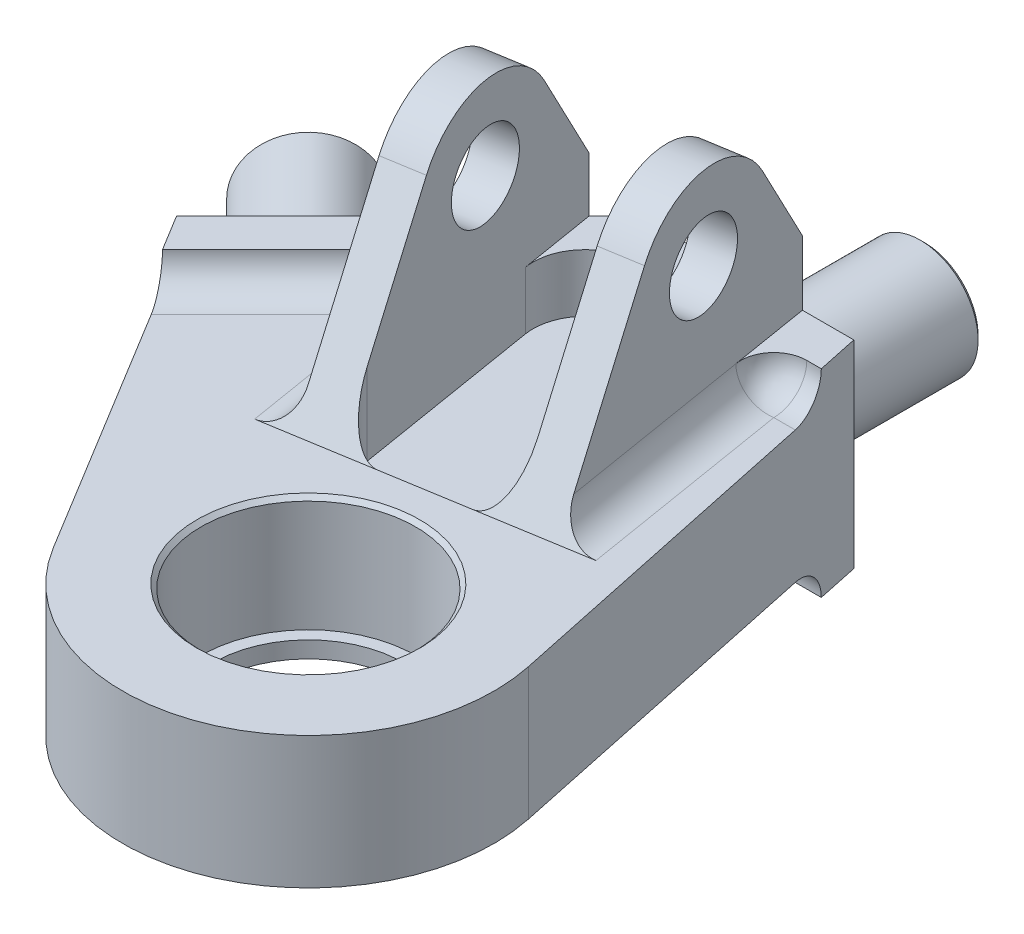
SolidWorks part; units mm, degrees
material "1.0545 (S355N)"
ref_plane "Płaszczyzna przednia" through (0, 0, 0) normal (0, 0, 1) x (1, 0, 0)
ref_plane "Płaszczyzna górna" through (0, 0, 0) normal (0, 1, 0) x (1, 0, 0)
ref_plane "Płaszczyzna prawa" through (0, 0, 0) normal (1, 0, 0) x (0, 0, -1)
sketch3d "Szkic 3D1"
  line L0 (0, 0, 0) -> (-3.9895, 1.5605, -24.295)
  line L1 (-3.9895, 1.5605, -24.295) -> (-3.9895, 27.3265, -24.295)
  line L2 (0, 0, 0) -> (0, 0, -24.5157) construction
  dimension "D1" = 10
ref_plane "Płaszczyzna1" through (0, 0, 0) normal (0.9868, 0, -0.162) x (-0.162, 0, -0.9868)
sketch "Szkic1" plane through (0, 0, 0) normal (0, 1, 0) x (1, 0, 0)
  line L0 (-39.9158, 22.2381) -> (-19.2096, -11.7149)
  line L1 (12.5, 49.6539) -> (22.0134, 4.6539)
  line L2 (0, 0) -> (0, 49.6539) construction
  line L3 (0, 0) -> (-31.0769, 31.0769) construction
  line L4 (-39.9158, 22.2381) -> (-12.5, 49.6539)
  line L5 (-12.5, 49.6539) -> (12.5, 49.6539)
  line L6 (-39.9158, 22.2381) -> (-42.5944, 26.6305)
  line L7 (-42.5944, 26.6305) -> (-14.5711, 54.6539)
  line L8 (-14.5711, 54.6539) -> (11.443, 54.6539)
  line L9 (12.5, 49.6539) -> (11.443, 54.6539)
  circle A0 centre (0, 0) radius 13
  arc A1 (-19.2096, -11.7149) -> (22.0134, 4.6539) centre (0, 0) ccw
  circle A2 centre (0, 0) radius 11.5
  point P14 (0, 49.6539)
  dimension "D3" = 26
  dimension "D4" = 45
  dimension "D8" = 23
  dimension "D1" = 45
  dimension "D2" = 25
  dimension "D5" = 12.5
  dimension "D6" = 5
  dimension "D7" = 5
  dimension "D9" = 45
extrude "Dodanie-wyciągnięcie1" add sketch "Szkic1" along normal mid plane 16 contours L0 A1 L1 L5 L4 A0 | A0 A2 region at (-5.7297, 0, -17.1806) region at (-12.6323, 0, 0)
sketch "Szkic2" plane through (0, 0, 0) normal (0.9868, 0, -0.162) x (-0.162, 0, -0.9868)
  line L0 (17.186, 8) -> (29.8877, 30)
  line L1 (46.9721, 8) -> (1.0252, 8) construction
  line L4 (17.186, 8) -> (17.186, 34.9977) construction
  line L5 (57.0232, 8) -> (57.0232, 32.5892) construction
  line L6 (17.186, 8) -> (57.0232, 8)
  line L8 (57.0232, 13) -> (47.2082, 30)
  line L9 (57.0232, 13) -> (57.0232, 8)
  line L10 (51.0232, 8) -> (51.0232, -8) construction
  arc A0 (47.2082, 30) -> (29.8877, 30) centre (38.5479, 25) ccw
  circle A1 centre (38.5479, 25) radius 5
  dimension "D1" = 10
  dimension "D2" = 10
  dimension "D3" = 17
  dimension "D4" = 30
  dimension "D5" = 5
  dimension "D6" = 30
  dimension "D7" = 6
extrude "Dodanie-wyciągnięcie2" add sketch "Szkic2" along normal mid plane 28
extrude "Dodanie-wyciągnięcie3" add sketch "Szkic1<5>" along normal mid plane 24 contours L5 L9 L8 L7 L6 L4 region at (-40.7094, 0, -24.7671)
sketch "Szkic1<5>" plane through (0, 0, 0) normal (0, 1, 0) x (1, 0, 0) same geometry as "Szkic1"
extrude "Wytnij-wyciągnięcie1" cut sketch "Szkic1<3>" against normal blind 6 and the other way through all contours A0 A2 region at (-12.6323, 0, 0)
sketch "Szkic1<3>" plane through (0, 0, 0) normal (0, 1, 0) x (1, 0, 0) same geometry as "Szkic1"
sketch "Szkic3" plane through (0, 8, 0) normal (0, 1, 0) x (1, 0, 0)
  line L0 (-11.6659, 15.5005) -> (6.0962, 18.4172)
  line L1 (6.0962, 18.4172) -> (0.9668, 49.6539)
  line L3 (11.0301, 19.2274) -> (-16.5998, 14.6903) construction
  line L4 (0, 0) -> (-9.9973, 60.8804) construction
  line L5 (-11.6659, 15.5005) -> (-16.6009, 45.553)
  line L6 (6.0337, 49.6539) -> (-9.9095, 49.6539)
  line L7 (-20.9532, 41.2007) -> (-16.6009, 45.553)
  line L8 (-39.9158, 22.2381) -> (-20.9532, 41.2007) construction
  line L9 (-18.658, 27.2241) -> (-16.5998, 14.6903) construction
  line L11 (5.2127, 54.6539) -> (4.5748, 58.5381)
  line L12 (4.5748, 58.5381) -> (-23.0551, 54.0009) construction
  line L13 (5.2127, 54.6539) -> (4.5748, 58.5381) construction
  line L14 (4.5748, 58.5381) -> (-23.0551, 54.0009)
  line L15 (-23.0551, 54.0009) -> (-21.9505, 47.2744)
  line L16 (-21.9505, 47.2744) -> (-14.5711, 54.6539)
  line L17 (-14.5711, 54.6539) -> (5.2127, 54.6539)
  line L18 (0.9668, 49.6539) -> (0.1457, 54.6539)
  line L19 (-16.6009, 45.553) -> (-17.5983, 51.6267)
  arc A0 (-9.9095, 49.6539) -> (-16.0809, 42.3864) centre (-9.9095, 43.3998) ccw
  point P10 (-2.7849, 16.9588)
  line M12 (11.0301, 19.2274) -> (-16.5998, 14.6903)
  dimension "D1" = 5
extrude "Wytnij-wyciągnięcie2" cut sketch "Szkic3" along normal through all and the other way blind 3 contours L4 L1 L6 M12 | L0 L4 L6 L7 L5 region at (-9.7818, 8, -32.314) region at (-1.0031, 8, -33.6682)
extrude "Wytnij-wyciągnięcie3" cut sketch "Szkic3<3>" along normal through all from offset 4 contours L6 L4 L17 L16 L19 L7 | L4 L6 L18 L17 region at (-13.2628, 8, -51.0363) region at (-4.004, 8, -52.1539)
sketch "Szkic3<3>" plane through (0, 8, 0) normal (0, 1, 0) x (1, 0, 0) same geometry as "Szkic3"
extrude "Wytnij-wyciągnięcie4" cut sketch "Szkic3<4>" along normal through all contours L4 L17 L11 L14 | L17 L4 L14 L15 L16 region at (-18.2488, 8, -52.7517) region at (-1.1443, 8, -56.1068)
sketch "Szkic3<4>" plane through (0, 8, 0) normal (0, 1, 0) x (1, 0, 0) same geometry as "Szkic3"
sketch "Szkic4" plane through (0, 0, -54.6539) normal (0, 0, -1) x (-1, 0, 0)
  circle A0 centre (0, 0) radius 7
  dimension "D1" = 14
extrude "Dodanie-wyciągnięcie4" add sketch "Szkic4" along normal blind 20
sketch "Szkic5" plane through (-34.6125, 0, -34.6125) normal (-0.7071, 0, -0.7071) x (-0.7071, 0, 0.7071)
  circle A0 centre (0, 0) radius 7
  dimension "D1" = 14
extrude "Dodanie-wyciągnięcie5" add sketch "Szkic5" along normal blind 20
sketch "Szkic6" plane through (0, -8, 0) normal (0, -1, 0) x (1, 0, 0)
  line L0 (7.6358, -43.6539) -> (13.165, -17.5)
  line L1 (13.165, -17.5) -> (-7.2487, -17.5)
  line L2 (-7.2487, -17.5) -> (-21.3804, -3.3683)
  line L3 (-21.3804, -3.3683) -> (-32.3359, -21.3327)
  line L4 (-32.3359, -21.3327) -> (-10.0147, -43.6539)
  line L5 (-10.0147, -43.6539) -> (7.6358, -43.6539)
  line L6 (12.5, -49.6539) -> (22.0134, -4.6539) construction
  line L7 (-39.9158, -22.2381) -> (-19.2096, 11.7149) construction
  line L8 (-39.9158, -22.2381) -> (-12.5, -49.6539) construction
  line L9 (-12.5, -49.6539) -> (12.5, -49.6539) construction
  line L10 (-39.9158, -22.2381) -> (-12.5, -49.6539) construction
  line L11 (17.2567, -11.5) -> (-4.7635, -11.5) construction
  line L12 (-4.7635, -11.5) -> (-16.7988, 0.5354) construction
  circle A0 centre (0, 0) radius 11.5 construction
  dimension "D2" = 6
  dimension "D1" = 6
  dimension "D3" = 6
  dimension "D4" = 6
  dimension "D5" = 6
  dimension "D6" = 6
extrude "Wytnij-wyciągnięcie5" cut sketch "Szkic6" against normal blind 3
fillet "Zaokrąglenie1" radius 4 12 edges at (-12.5, -10, -49.6539) (-21.3804, -6.5, -3.3683) (-7.2487, -6.5, -17.5) (13.165, -6.5, -17.5) (7.6358, -6.5, -43.6539) (-10.0147, -6.5, -43.6539) (-32.3359, -6.5, -21.3327) (-20.9532, 10, -41.2007) (6.0962, 6.5, -18.4172) (-11.6659, 6.5, -15.5005) (0.9668, 8.5, -49.6539) (6.0337, 10, -49.6539)
fillet "Zaokrąglenie2" radius 4 9 edges at (-18.1449, 8, -24.0992) (-22.4118, 8, -36.6676) (-33.1906, 8, -28.9632) (11.6221, 8, -49.6539) (8.9136, 8, -32.1166) (7.6952, 8, -48.243) (-26.7937, -8, -35.3602) (-12.3739, -8, -49.3494) (0.8284, -8, -49.6539)
fillet "Zaokrąglenie3" radius 1 2 edges at (-39.5622, 0, -29.6627) (-7, 0, -54.6539)
chamfer "Sfazowanie1" distance 0.5 angle 45 3 edges at (0, 8, 13) (-53.7043, 0, -43.8049) (-7, 0, -74.6539)
equation "\"D5@Szkic1\"=\"D2@Szkic1\"/2"
equation "\"D7@Szkic1\"=\"D6@Szkic1\""
equation "\"D8@Szkic1\"=\"D3@Szkic1\"-3"
equation "\"D2\"= \"D1@Dodanie-wyciągnięcie1\" / 2 - 2"
equation "\"D1@Wytnij-wyciągnięcie1\"=\"D1@Dodanie-wyciągnięcie1\"/2 -2"
equation "\"D3@Szkic6\" = \"D1@Szkic6\""
equation "\"D2@Szkic6\" = \"D1@Szkic6\""
equation "\"D4@Szkic6\" = \"D1@Szkic6\""
equation "\"D5@Szkic6\" = \"D1@Szkic6\""
equation "\"D6@Szkic6\" = \"D1@Szkic6\""
